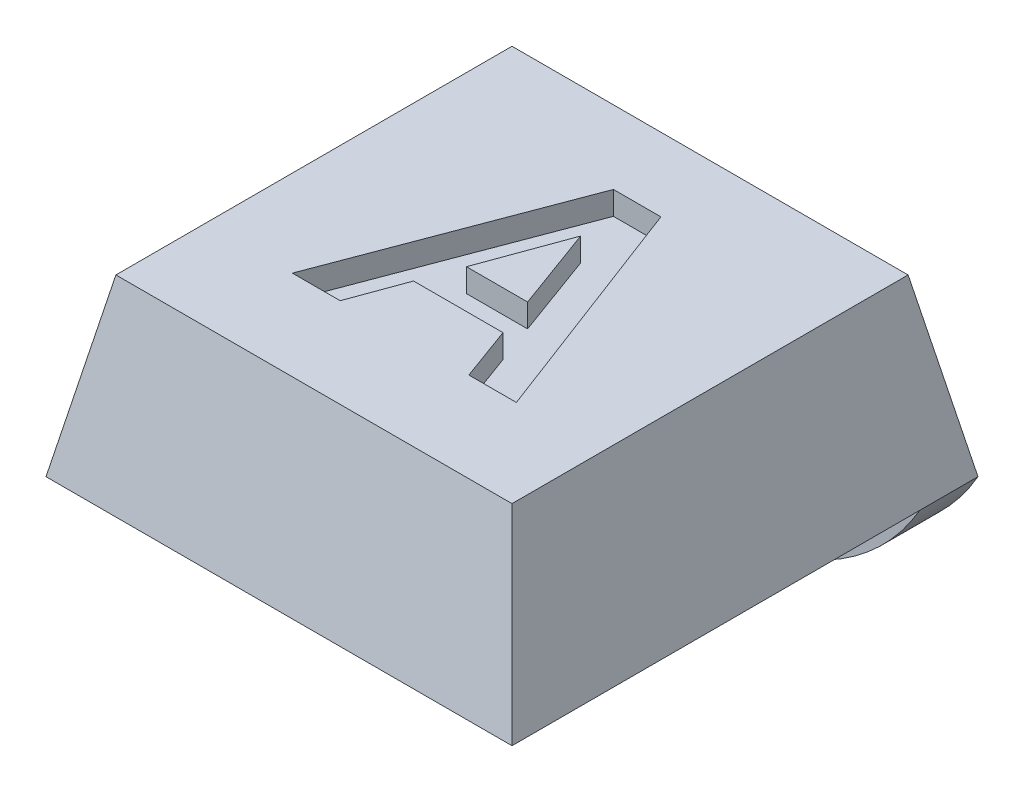
SolidWorks part; units mm, degrees
ref_plane "Front Plane" through (0, 0, 0) normal (0, 0, 1) x (1, 0, 0)
ref_plane "Top Plane" through (0, 0, 0) normal (0, 1, 0) x (1, 0, 0)
ref_plane "Right Plane" through (0, 0, 0) normal (1, 0, 0) x (0, 0, -1)
sketch "Sketch1" plane through (0, 0, 0) normal (0, 1, 0) x (1, 0, 0)
  line L1 (0, 0) -> (8, 0)
  line L2 (0, 0) -> (0, 8)
  line L3 (0, 8) -> (8, 8)
  line L4 (8, 0) -> (8, 8)
  dimension "D1" = 8
  dimension "D2" = 8
extrude "Boss-Extrude1" add sketch "Sketch1" along normal blind 3
sketch "Sketch2" plane through (0, 0, 0) normal (0, 0, 1) x (1, 0, 0)
  line L0 (0, 0) -> (0.6, 3)
  line L1 (0, 3) -> (8, 3) construction
  line L2 (0.6, 3) -> (0, 3)
  line L3 (0, 3) -> (0, 0)
  line L4 (8, 0) -> (7.4, 3)
  line L5 (7.4, 3) -> (8, 3)
  line L6 (8, 3) -> (8, 0)
  dimension "D1" = 0.6
  dimension "D2" = 0.6
extrude "Cut-Extrude1" cut sketch "Sketch2" against normal through all both and the other way through all
sketch "Sketch3" plane through (0, 0, 0) normal (1, 0, 0) x (0, 0, -1)
  line L0 (0, 0) -> (0.6, 3)
  line L1 (8, 3) -> (0, 3) construction
  line L2 (0.6, 3) -> (0, 3)
  line L3 (0, 3) -> (0, 0)
  line L4 (8, 3) -> (7.4, 3)
  line L5 (7.4, 3) -> (8, 0)
  line L6 (8, 3) -> (8, 0)
  dimension "D1" = 0.6
  dimension "D2" = 0.6
extrude "Cut-Extrude2" cut sketch "Sketch3" along normal blind 11
sketch "Sketch4" plane through (0, 0, 0) normal (0, -1, 0) x (1, 0, 0)
  line L0 (8, 0) -> (8, -8) construction
  line L3 (0, 0) -> (8, 0) construction
  circle A0 centre (4, -3.75) radius 1.8
  dimension "D1" = 3.6
  dimension "D2" = 4
  dimension "D3" = 3.75
extrude "Cut-Extrude3" cut sketch "Sketch4" against normal blind 0.8
sketch "Sketch5" plane through (0, 0, 0) normal (0, -1, 0) x (1, 0, 0)
  line L0 (8, 0) -> (8, -8) construction
  line L1 (0, -8) -> (8, -8)
  line L2 (0, -8) -> (0, -7)
  line L3 (0, -7) -> (8, -7)
  line L4 (8, -8) -> (8, -7)
  dimension "D1" = 1
extrude "Boss-Extrude2" add sketch "Sketch5" along normal blind 2
fillet "Fillet1" radius 4 2 edges at (8, -2, -7.5) (0, -2, -7.5)
sketch "Sketch6" plane through (0, 3, 0) normal (0, 1, 0) x (1, 0, 0)
  text T0 "A" font "Arial" height 4
extrude "Cut-Extrude4" cut sketch "Sketch6" against normal blind 0.4
